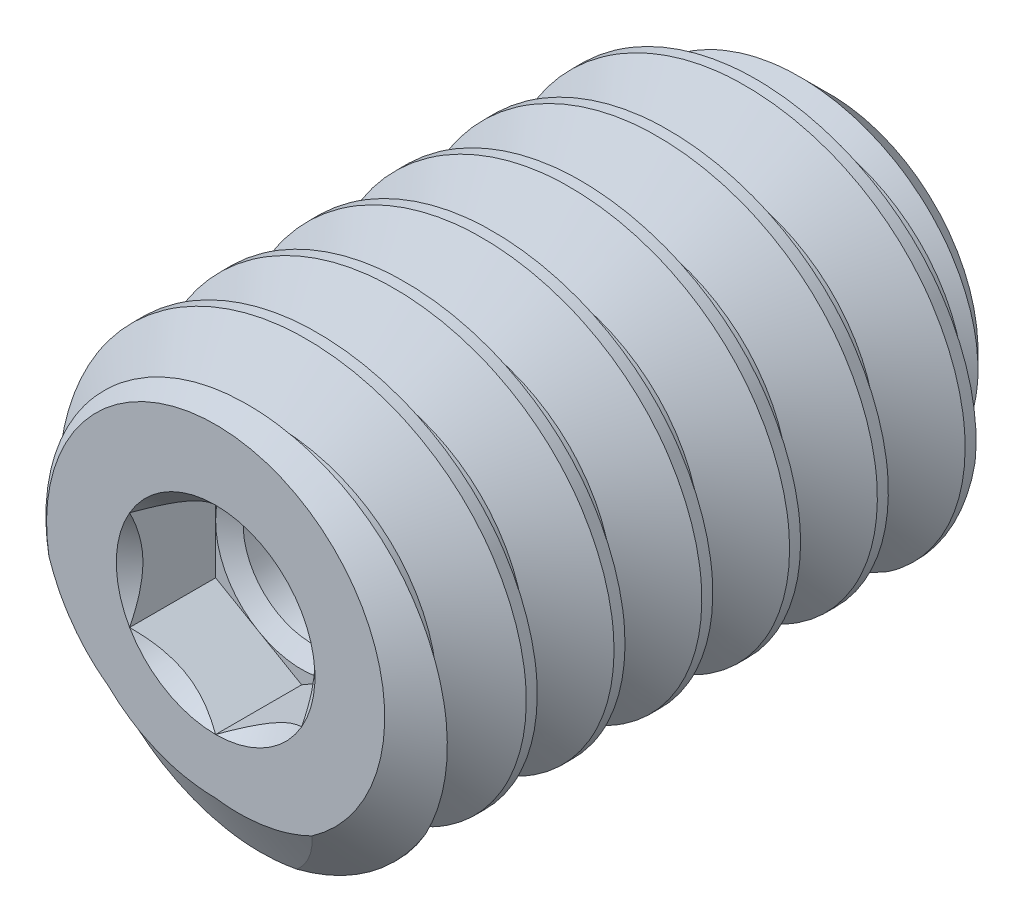
SolidWorks part; units mm, degrees
ref_plane "Front" through (0, 0, 0) normal (0, 0, 1) x (1, 0, 0)
ref_plane "Top" through (0, 0, 0) normal (0, 1, 0) x (1, 0, 0)
ref_plane "Right" through (0, 0, 0) normal (1, 0, 0) x (0, 0, -1)
sketch "Sketch22" plane through (0, 0, 0) normal (1, 0, 0) x (0, 0, -1)
  line L0 (-1.5875, 0) -> (-1.5875, 0.8738)
  line L1 (-1.5875, 0.8738) -> (-1.4345, 1.0922)
  line L2 (-1.4345, 1.0922) -> (1.2598, 1.0922)
  line L3 (1.2598, 1.0922) -> (1.5875, 0.7645)
  line L4 (0, 1.0922) -> (0, -1.0922) construction
  line L5 (1.2598, 0) -> (-1.5875, 0)
  line L6 (1.5875, 0.7645) -> (1.5875, 0.5461)
  line L8 (1.2598, 1.0922) -> (1.2598, 0) construction
  line L10 (-1.5875, 0) -> (1.5875, 0) construction
  line L11 (1.5875, 0.5461) -> (1.5875, -0.5461) construction
  arc A0 (1.2598, 0) -> (1.5875, 0.5461) centre (1.8788, 0) cw
  dimension "Length" = 3.175
  dimension "D3" = 35
  dimension "D1" = 45
  dimension "D5" = 1.0922
  dimension "Dia" = 2.1844
  dimension "D4" = 0.3277
revolve "Revolve1" add sketch "Sketch22" angle 360 about L5
ref_plane "Plane1" through (0, 0, -1.5875) normal (0, 0, 1) x (1, 0, 0)
sketch "Sketch27" plane through (0, 0, -1.5875) normal (0, 0, 1) x (1, 0, 0)
  circle A0 centre (0, 0) radius 1.0922 construction
  circle A1 centre (0, 0) radius 1.0922
curve "Helix/Spiral1" pitch 0.4536 height 3.6286 radius 1.0922 centre (0, 0, -1.5875) axis (0, 0, 1) start towards (0, 1, 0)
sketch "Sketch28" plane through (0, 0, 0) normal (1, 0, 0) x (0, 0, -1)
  line L0 (1.5875, 1.0922) -> (1.9844, 1.0922)
  line L1 (1.9844, 1.0922) -> (1.8143, 0.7976)
  line L2 (1.8143, 0.7976) -> (1.7576, 0.7976)
  line L3 (1.7576, 0.7976) -> (1.5875, 1.0922)
  line L4 (1.6725, 0.9449) -> (1.8993, 0.9449) construction
  line L5 (-1.4345, 1.0922) -> (1.2598, 1.0922) construction
  dimension "D1" = 0.0567
  dimension "D3" = 60
sweep "Cut-Sweep2" cut profiles "Sketch28" path "Helix/Spiral1" align with end faces yes
sketch "Sketch23" plane through (0, 0, 1.5875) normal (0, 0, 1) x (1, 0, 0)
  line L1 (0, 0.5133) -> (-0.4445, 0.2566)
  line L2 (-0.4445, 0.2566) -> (-0.4445, -0.2566)
  line L3 (-0.4445, -0.2566) -> (0, -0.5133)
  line L4 (0, -0.5133) -> (0.4445, -0.2566)
  line L5 (0.4445, -0.2566) -> (0.4445, 0.2566)
  line L6 (0.4445, 0.2566) -> (0, 0.5133)
  circle A0 centre (0, 0) radius 0.4445 construction
extrude "Cut-Extrude10" cut sketch "Sketch23" against normal blind 0.4445
sketch "Sketch24" plane through (0, 0, 1.5875) normal (0, 0, 1) x (1, 0, 0)
  circle A0 centre (0, 0) radius 0.5133
extrude "Cut-Extrude11" cut sketch "Sketch24" against normal through all draft 45
sketch "Sketch26" plane through (0, 0, 1.143) normal (0, 0, 1) x (1, 0, 0)
  circle A0 centre (0, 0) radius 0.4445 construction
  circle A1 centre (0, 0) radius 0.4445
extrude "Cut-Extrude12" cut sketch "Sketch26" against normal through all draft 59
sketch "Sketch31" plane through (0, 0, 0) normal (0, 0, 1) x (1, 0, 0)
  circle A0 centre (0, 0) radius 0.3556
  dimension "vent hole" = 0.7112
extrude "Extrude1" cut sketch "Sketch31" against normal through all and the other way through all
sketch "Sketch30" plane through (0, 0, 0) normal (1, 0, 0) x (0, 0, -1)
  line L0 (-1.4345, 1.0922) -> (1.2598, 1.0922) construction
  line L1 (-1.5875, 0) -> (-1.5875, 0.8738) construction
  line L4 (1.5875, 1.2327) -> (1.5875, -1.2327) construction
  point P0 (-1.5875, 1.0922)
  point P1 (1.5875, 1.0922)
  point P2 (1.5875, -1.0922)
  point P12 (0.9071, -1.0922)
  dimension "D2" = 0.6804
sketch "Sketch32" plane through (0, 0, 0) normal (1, 0, 0) x (0, 0, -1)
  line L2 (1.3722, 0.3556) -> (-1.0896, 0.3556)
  line L3 (-1.0896, -0.3556) -> (1.3722, -0.3556)
  line L4 (-1.143, -0.4445) -> (-1.0896, -0.3556) construction
  line L5 (-1.0896, 0.3556) -> (-1.143, 0.4445) construction
  line L6 (-1.143, -0.4445) -> (-1.0896, -0.3556)
  line L7 (-1.0896, 0.3556) -> (-1.143, 0.4445)
  line L8 (-1.143, -0.5133) -> (-1.5875, -0.5133) construction
  line L9 (-1.143, 0.5133) -> (-1.5875, 0.5133) construction
  line L10 (-1.143, -0.5133) -> (-1.5875, -0.5133)
  line L11 (-1.143, 0.5133) -> (-1.5875, 0.5133)
  line L12 (-1.143, -0.4445) -> (-1.143, -0.5133)
  line L13 (-1.143, 0.4445) -> (-1.143, 0.5133)
  line L14 (-1.0896, -0.3556) -> (1.3722, -0.3556) construction
  line L15 (1.3722, 0.3556) -> (-1.0896, 0.3556) construction
  line L17 (1.5875, 1.2327) -> (1.5875, -1.2327) construction
  arc A1 (1.5875, 0.5461) -> (1.3722, 0.3556) centre (1.8788, 0) ccw construction
  arc A2 (1.5875, 0.5461) -> (1.3722, 0.3556) centre (1.8788, 0) ccw
  arc A3 (1.3722, -0.3556) -> (1.5875, -0.5461) centre (1.8788, 0) ccw
equation "\"D1@Sketch28\" = \"D4@Helix/Spiral1\" * .125"
equation "\"D2@Sketch28\" = \"D4@Helix/Spiral1\" * .5"
equation "\"D3@Helix/Spiral1\" = \"Length@Sketch22\" + \"D4@Helix/Spiral1\""
equation "\"D2@Sketch22\" = \"Dia@Sketch22\" * .1"
equation "\"D2@Sketch30\" = \"D4@Helix/Spiral1\" * 1.5"
equation "\"hex Depth@Cut-Extrude10\" = \"Hex@Sketch23\" * .5"
equation "\"D5@Sketch22\" = \"Dia@Sketch22\" * .5"
equation "\"D4@Sketch22\" = \"D5@Sketch22\" * .3"
